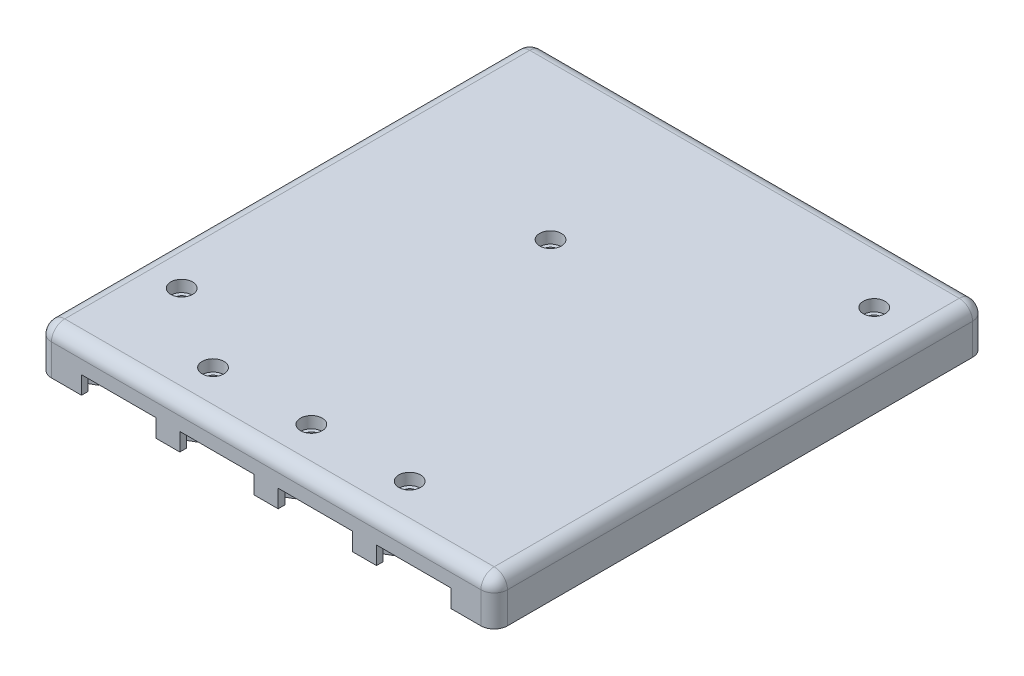
SolidWorks part; units mm, degrees
ref_plane "Front Plane" through (0, 0, 0) normal (0, 0, 1) x (1, 0, 0)
ref_plane "Top Plane" through (0, 0, 0) normal (0, 1, 0) x (1, 0, 0)
ref_plane "Right Plane" through (0, 0, 0) normal (1, 0, 0) x (0, 0, -1)
sketch "Sketch1" plane through (0, 0, 0) normal (0, 1, 0) x (1, 0, 0)
  line L0 (-1, -1) -> (-1, 15.7637) construction
  line L1 (-6, -6) -> (79.8, -6)
  line L2 (-6, -6) -> (-6, 86.5)
  line L3 (-6, 86.5) -> (79.8, 86.5)
  line L4 (79.8, -6) -> (79.8, 86.5)
  line L5 (-1, -1) -> (16.6536, -1) construction
  circle A0 centre (2.5, 12.5) radius 2.05
  circle A1 centre (18.4, 2.5) radius 2.05
  circle A2 centre (36.9, 2.5) radius 2.05
  circle A3 centre (55.4, 2.5) radius 2.05
  circle A4 centre (29.3, 55.1) radius 2.05
  circle A5 centre (70.8, 74.5) radius 2.05
  dimension "D16" = 4.1
  dimension "D1" = 92.5
  dimension "D2" = 85.8
  dimension "D3" = 5
  dimension "D4" = 1
  dimension "D5" = 1
  dimension "D6" = 5
  dimension "D7" = 12.5
  dimension "D8" = 2.5
  dimension "D9" = 18.4
  dimension "D10" = 18.5
  dimension "D11" = 18.5
  dimension "D12" = 55.1
  dimension "D13" = 29.3
  dimension "D14" = 41.5
  dimension "D15" = 74.5
  dimension "D17" = 2.5
extrude "Boss-Extrude1" add sketch "Sketch1" along normal blind 3.175
sketch "Sketch2" plane through (0, 0, 0) normal (0, 1, 0) x (1, 0, 0)
  line L0 (2.5, 7.5) -> (-1, 7.5)
  line L1 (-6, 86.5) -> (79.8, 86.5)
  line L2 (-6, 86.5) -> (-6, -6)
  line L3 (-6, -6) -> (79.8, -6)
  line L4 (79.8, 86.5) -> (79.8, -6)
  line L5 (-1, 7.5) -> (-1, -1)
  line L6 (-1, -1) -> (13.4, -1)
  line L7 (13.4, -1) -> (13.4, 2.5)
  line L8 (2.5, 17.5) -> (-1, 17.5)
  line L9 (-1, 17.5) -> (-1, 81.5)
  line L10 (-1, 81.5) -> (65.8, 81.5)
  line L11 (65.8, 74.5) -> (65.8, 81.5)
  line L13 (70.8, 69.5) -> (74.8, 69.5)
  line L14 (74.8, 69.5) -> (74.8, -1)
  line L15 (74.8, -1) -> (60.4, -1)
  line L16 (60.4, -1) -> (60.4, 2.5)
  line L17 (23.4, 2.5) -> (23.4, -1)
  line L18 (23.4, -1) -> (31.9, -1)
  line L19 (31.9, -1) -> (31.9, 2.5)
  line L20 (41.9, 2.5) -> (41.9, -1)
  line L21 (41.9, -1) -> (50.4, -1)
  line L22 (50.4, -1) -> (50.4, 2.5)
  circle A0 centre (2.5, 12.5) radius 1.35
  circle A1 centre (18.4, 2.5) radius 1.35
  circle A2 centre (36.9, 2.5) radius 1.35
  circle A3 centre (55.4, 2.5) radius 1.35
  circle A4 centre (29.3, 55.1) radius 1.35
  circle A5 centre (70.8, 74.5) radius 1.35
  circle A6 centre (29.3, 55.1) radius 3.35
  arc A7 (2.5, 17.5) -> (2.5, 7.5) centre (2.5, 12.5) cw
  arc A8 (13.4, 2.5) -> (23.4, 2.5) centre (18.4, 2.5) cw
  arc A9 (31.9, 2.5) -> (41.9, 2.5) centre (36.9, 2.5) cw
  arc A10 (50.4, 2.5) -> (60.4, 2.5) centre (55.4, 2.5) cw
  arc A11 (65.8, 74.5) -> (70.8, 69.5) centre (70.8, 74.5) ccw
  dimension "D1" = 2.7
  dimension "D2" = 6.7
  dimension "D3" = 5
  dimension "D4" = 5
  dimension "D5" = 5
  dimension "D6" = 5
  dimension "D7" = 5
extrude "Boss-Extrude2" add sketch "Sketch2" against normal blind 1.905 contours L4 L1 L2 L3 A0 A1 A2 A3 A5 L11 A11 L13 L14 L15 L16 A10 L22 L21 L20 A9 L19 L18 L17 A8 L7 L6 L5 L0 A7 L8 L9 L10 | A6 A4 region at (36.9, 0, -85.2383) region at (26.0448, 0, -55.1)
extrude "Boss-Extrude3" add sketch "Sketch2<3>" along normal blind 1 contours L4 L1 L2 L3 A0 A1 A2 A3 A5 L11 A11 L13 L14 L15 L16 A10 L22 L21 L20 A9 L19 L18 L17 A8 L7 L6 L5 L0 A7 L8 L9 L10 | A6 A4 region at (36.9, 0, -85.2383) region at (26.0448, 0, -55.1)
sketch "Sketch2<3>" plane through (0, 0, 0) normal (0, 1, 0) x (1, 0, 0) same geometry as "Sketch2"
ref_plane "Plane1" through (0, -1.905, 0) normal (0, -1, 0) x (-1, 0, 0)
sketch "Sketch3" plane through (0, -1.905, 0) normal (0, -1, 0) x (-1, 0, 0)
  line L1 (6, 86.5) -> (-79.8, 86.5)
  line L2 (6, 86.5) -> (6, -6)
  line L3 (6, -6) -> (-79.8, -6)
  line L4 (-79.8, 86.5) -> (-79.8, -6)
  line L5 (1, 81.5) -> (-74.8, 81.5)
  line L6 (1, 81.5) -> (1, -1)
  line L7 (1, -1) -> (-74.8, -1)
  line L8 (-74.8, 81.5) -> (-74.8, -1)
  dimension "D1" = 5
  dimension "D2" = 5
  dimension "D3" = 5
  dimension "D4" = 5
extrude "Boss-Extrude4" add sketch "Sketch3" along normal blind 3.3
sketch "Sketch4" plane through (0, 0, 0) normal (0, 0, 1) x (1, 0, 0)
  line L0 (79.8, -5.205) -> (-6, -5.205) construction
  line L1 (2.15, -1.845) -> (16.15, -1.845)
  line L2 (2.15, -1.845) -> (2.15, -8.595)
  line L3 (2.15, -8.595) -> (16.15, -8.595)
  line L4 (16.15, -1.845) -> (16.15, -8.595)
  line L5 (20.65, -1.845) -> (34.65, -1.845)
  line L6 (20.65, -1.845) -> (20.65, -8.595)
  line L7 (20.65, -8.595) -> (34.65, -8.595)
  line L8 (34.65, -1.845) -> (34.65, -8.595)
  line L9 (39.15, -1.845) -> (53.15, -1.845)
  line L10 (39.15, -1.845) -> (39.15, -8.595)
  line L11 (39.15, -8.595) -> (53.15, -8.595)
  line L12 (53.15, -1.845) -> (53.15, -8.595)
  line L13 (57.65, -1.845) -> (71.65, -1.845)
  line L14 (57.65, -1.845) -> (57.65, -8.595)
  line L15 (57.65, -8.595) -> (71.65, -8.595)
  line L16 (71.65, -1.845) -> (71.65, -8.595)
  point P16 (9.15, -1.845)
  point P17 (27.65, -1.845)
  point P18 (46.15, -1.845)
  point P19 (64.65, -1.845)
  dimension "D1" = 14
  dimension "D2" = 14
  dimension "D3" = 14
  dimension "D4" = 14
  dimension "D5" = 9.15
  dimension "D6" = 18.5
  dimension "D7" = 18.5
  dimension "D8" = 18.5
  dimension "D9" = 6.75
  dimension "D10" = 3.36
extrude "Cut-Extrude1" cut sketch "Sketch4" along normal through all
sketch "Sketch5" plane through (0, 0, 0) normal (0, 0, 1) x (1, 0, 0)
  line L0 (-1, -5.205) -> (74.8, -5.205) construction
  line L1 (53, -3.205) -> (63, -3.205)
  line L2 (53, -3.205) -> (53, -9.205)
  line L3 (53, -9.205) -> (63, -9.205)
  line L4 (63, -3.205) -> (63, -9.205)
  point P4 (58, -3.205)
  dimension "D1" = 58
  dimension "D2" = 10
  dimension "D3" = 6
  dimension "D4" = 2
extrude "Cut-Extrude2" cut sketch "Sketch5" against normal through all
ref_plane "Plane2" through (-6, 0, 0) normal (-1, 0, 0) x (0, 0, 1)
sketch "Sketch6" plane through (-6, 0, 0) normal (-1, 0, 0) x (0, 0, 1)
  line L0 (-59.6, 0) -> (-59.6, -8.5)
  line L1 (-59.6, 0) -> (-50.6, 0)
  line L2 (-59.6, -8.5) -> (-59.1311, -8.5)
  line L3 (-50.6, 0) -> (-50.6, -8.5)
  line L4 (-50.6, -8.5) -> (-51.0689, -8.5)
  arc A0 (-59.1311, -8.5) -> (-51.0689, -8.5) centre (-55.1, -10.5) cw
  point P3 (-55.1, 0)
  dimension "D1" = 4.5
  dimension "D2" = 10.5
  dimension "D3" = 55.1
  dimension "D4" = 9
  dimension "D5" = 2
extrude "Boss-Extrude5" add sketch "Sketch6" against normal blind 3.5
fillet "Fillet1" radius 2.5 1 edges at (79.8, -1.015, 6)
fillet "Fillet2" radius 2.5 1 edges at (79.8, -1.015, -86.5)
fillet "Fillet3" radius 2.5 1 edges at (-6, -1.015, -86.5)
fillet "Fillet4" radius 2.5 1 edges at (-6, -1.015, 6)
fillet "Fillet5" radius 2.5 8 edges at (79.0678, 3.175, -85.7678) (79.8, 3.175, -40.25) (79.0678, 3.175, 5.2678) (36.9, 3.175, 6) (-5.2678, 3.175, 5.2678) (-6, 3.175, -40.25) (-5.2678, 3.175, -85.7678) (36.9, 3.175, -86.5)
ref_plane "Plane3" through (0, -5.205, 0) normal (0, -1, 0) x (-1, 0, 0)
sketch "Sketch7" plane through (0, -5.205, 0) normal (0, -1, 0) x (-1, 0, 0)
  line L0 (-2.15, -3.75) -> (-0.4, -3.75) construction
  line L2 (-2.15, -2.75) -> (-0.4, -3.75)
  line L3 (-2.15, -6) -> (-2.15, -1) construction
  line L4 (-0.4, -3.75) -> (-2.15, -4.75)
  line L5 (-2.15, -4.75) -> (-2.15, -2.75)
  line L6 (-16.15, -2.75) -> (-17.9, -3.75)
  line L7 (-16.15, -1) -> (-16.15, -6) construction
  line L8 (-17.9, -3.75) -> (-16.15, -4.75)
  line L9 (-16.15, -4.75) -> (-16.15, -2.75)
  line L10 (-20.65, -2.75) -> (-18.9, -3.75)
  line L11 (-20.65, -6) -> (-20.65, 0) construction
  line L12 (-18.9, -3.75) -> (-20.65, -4.75)
  line L13 (-20.65, -6) -> (-20.65, -1) construction
  line L14 (-20.65, -4.75) -> (-20.65, -2.75)
  line L15 (-34.65, -2.75) -> (-36.4, -3.75)
  line L16 (-34.65, -6) -> (-34.65, 0) construction
  line L17 (-36.4, -3.75) -> (-34.65, -4.75)
  line L18 (-34.65, -1) -> (-34.65, -6) construction
  line L19 (-34.65, -4.75) -> (-34.65, -2.75)
  line L20 (-39.15, -2.75) -> (-39.15, -4.75)
  line L21 (-39.15, -6) -> (-39.15, 0) construction
  line L22 (-39.15, -4.75) -> (-37.4, -3.75)
  line L23 (-37.4, -3.75) -> (-39.15, -2.75)
  line L24 (-53.15, -2.75) -> (-53.15, -4.75)
  line L25 (-53.15, -1) -> (-53.15, -6) construction
  line L26 (-53.15, -4.75) -> (-54.9, -3.75)
  line L27 (-54.9, -3.75) -> (-53.15, -2.75)
  line L28 (-57.65, -4.75) -> (-55.9, -3.75)
  line L29 (-57.65, -6) -> (-57.65, -1) construction
  line L30 (-55.9, -3.75) -> (-57.65, -2.75)
  line L31 (-57.65, -2.75) -> (-57.65, -4.75)
  line L32 (-71.65, -2.75) -> (-73.4, -3.75)
  line L33 (-71.65, -6) -> (-71.65, -1) construction
  line L34 (-73.4, -3.75) -> (-71.65, -4.75)
  line L35 (-71.65, -4.75) -> (-71.65, -2.75)
  dimension "D1" = 1.75
  dimension "D2" = 2
  dimension "D3" = 1.75
  dimension "D4" = 1.75
  dimension "D5" = 1.75
  dimension "D6" = 1.75
  dimension "D7" = 1.75
  dimension "D8" = 1.75
  dimension "D9" = 1.75
  dimension "D10" = 3.75
extrude "Cut-Extrude3" cut sketch "Sketch7" against normal blind 3.36
sketch "Sketch8" plane through (0, 0, 0) normal (1, 0, 0) x (0, 0, -1)
  line L0 (-4.75, -1.9) -> (-2.75, -1.9)
  line L1 (-2.75, -1.9) -> (-3.75, -0.15)
  line L2 (-3.75, -0.15) -> (-4.75, -1.9)
  line L3 (-3.75, -1.9) -> (-3.75, -0.15) construction
  dimension "D1" = 1.75
  dimension "D2" = 2
  dimension "D3" = 1.9
  dimension "D4" = 3.75
extrude "Cut-Extrude4" cut sketch "Sketch8" along normal blind 75
ref_plane "Plane4" through (0, 0, 6) normal (0, 0, 1) x (1, 0, 0)
sketch "Sketch10" plane through (0, 0, 6) normal (0, 0, 1) x (1, 0, 0)
  line L1 (2.15, -1.845) -> (-2.351, -1.845)
  line L2 (2.15, -1.845) -> (2.15, 0.155)
  line L3 (2.15, 0.155) -> (-2.351, 0.155)
  line L4 (-2.351, -1.845) -> (-2.351, 0.155)
  line L5 (20.65, -1.845) -> (16.149, -1.845)
  line L6 (20.65, -1.845) -> (20.65, 0.155)
  line L7 (20.65, 0.155) -> (16.149, 0.155)
  line L8 (16.149, -1.845) -> (16.149, 0.155)
  line L9 (39.15, -1.845) -> (34.649, -1.845)
  line L10 (39.15, -1.845) -> (39.15, 0.155)
  line L11 (39.15, 0.155) -> (34.649, 0.155)
  line L12 (34.649, -1.845) -> (34.649, 0.155)
  line L13 (57.65, -1.845) -> (53.149, -1.845)
  line L14 (57.65, -1.845) -> (57.65, 0.155)
  line L15 (57.65, 0.155) -> (53.149, 0.155)
  line L16 (53.149, -1.845) -> (53.149, 0.155)
  line L17 (71.65, -1.845) -> (76.151, -1.845)
  line L18 (71.65, -1.845) -> (71.65, 0.155)
  line L19 (71.65, 0.155) -> (76.151, 0.155)
  line L20 (76.151, -1.845) -> (76.151, 0.155)
  dimension "D1" = 2
  dimension "D2" = 4.501
extrude "Boss-Extrude6" add sketch "Sketch10" against normal blind 5
sketch "Sketch13" plane through (0, 0, 0) normal (1, 0, 0) x (0, 0, -1)
  circle A0 centre (55.1, -10.95) radius 6.35
  dimension "D1" = 12.7
  dimension "D2" = 55.1
  dimension "D3" = 10.95
extrude "Cut-Extrude5" cut sketch "Sketch13" against normal blind 2.5
